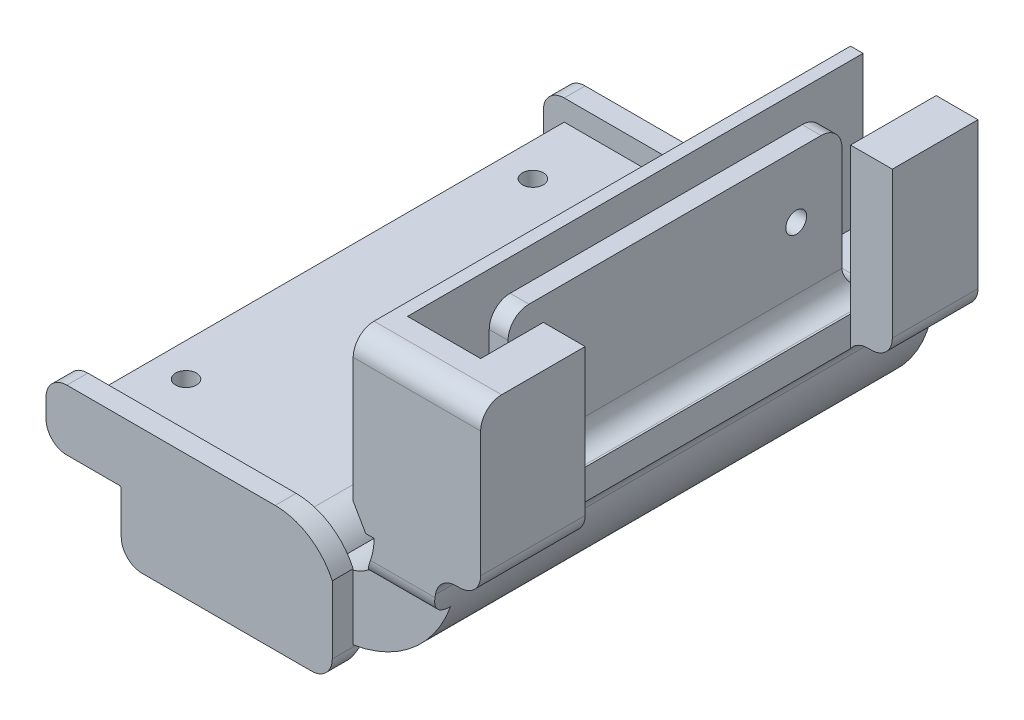
SolidWorks part; units mm, degrees
ref_plane "Alzado" through (0, 0, 0) normal (0, 0, 1) x (1, 0, 0)
ref_plane "Planta" through (0, 0, 0) normal (0, 1, 0) x (1, 0, 0)
ref_plane "Vista lateral" through (0, 0, 0) normal (1, 0, 0) x (0, 0, -1)
sketch "Croquis1" plane through (0, 0, 0) normal (0, 0, 1) x (1, 0, 0)
  line L0 (0, 0) -> (0, -5)
  line L1 (15, -20) -> (337, -20)
  line L2 (352, -5) -> (352, 0)
  line L3 (-15, 0) -> (-15, -5)
  line L4 (15, -35) -> (337, -35)
  line L5 (367, -5) -> (367, 0)
  line L6 (-15, 0) -> (0, 0)
  line L7 (352, 0) -> (367, 0)
  arc A0 (352, -5) -> (337, -20) centre (337, -5) cw
  arc A1 (0, -5) -> (15, -20) centre (15, -5) ccw
  arc A2 (-15, -5) -> (15, -35) centre (15, -5) ccw
  arc A3 (367, -5) -> (337, -35) centre (337, -5) cw
  dimension "D1" = 15
  dimension "D2" = 5
  dimension "D4" = 352
  dimension "D3" = 15
extrude "Saliente-Extruir1" add sketch "Croquis1" along normal blind 103
sketch "Croquis2" plane through (0, 0, 0) normal (0, 1, 0) x (1, 0, 0)
  line L0 (0, -103) -> (0, 0) construction
  line L1 (-10, -25.1459) -> (-5, -25.1459)
  line L2 (-10, -25.1459) -> (-10, -75.1459)
  line L3 (-10, -75.1459) -> (-5, -75.1459)
  line L4 (-5, -25.1459) -> (-5, -75.1459)
  line L5 (357, -11.55) -> (362, -11.55)
  line L6 (357, -11.55) -> (357, -91.45)
  line L7 (357, -91.45) -> (362, -91.45)
  line L8 (362, -11.55) -> (362, -91.45)
  line L9 (352, -103) -> (352, 0) construction
  line L10 (352, 0) -> (352, -103) construction
  point P12 (362, -51.5)
  point P17 (352, -51.5)
  dimension "D1" = 5
  dimension "D2" = 50
  dimension "D3" = 5
  dimension "D4" = 79.9
  dimension "D5" = 5
  dimension "D6" = 5
extrude "Saliente-Extruir2" add sketch "Croquis2" along normal blind 35
fillet "Redondeo1" radius 5 8 edges at (362, 0, 51.5) (359.5, 0, 91.45) (357, 0, 51.5) (359.5, 0, 11.55) (-7.5, 0, 25.1459) (-10, 0, 50.1459) (-7.5, 0, 75.1459) (-5, 0, 50.1459)
fillet "Redondeo2" radius 5 4 edges at (-7.5, 35, 25.1459) (-7.5, 35, 75.1459) (359.5, 35, 11.55) (359.5, 35, 91.45)
ref_plane "Plano1" through (15, 0, 0) normal (1, 0, 0) x (0, 0, -1)
sketch "Croquis3" plane through (15, 0, 0) normal (1, 0, 0) x (0, 0, -1)
  line L0 (-103, -35) -> (0, -35) construction
  line L1 (-76.5, -35) -> (-70.5, -35)
  line L2 (-76.5, -35) -> (-76.5, -43)
  line L3 (-76.5, -43) -> (-26.5, -43)
  line L4 (-26.5, -35) -> (-26.5, -43)
  line L5 (-103, -35) -> (-70.5, -35) construction
  line L6 (-51.5, -33) -> (-51.5, -5) construction
  line L7 (-103, -5) -> (0, -5) construction
  line L8 (-32.5, -35) -> (-26.5, -35)
  line L10 (-70.5, -35) -> (-70.5, -39)
  line L11 (-70.5, -39) -> (-32.5, -39)
  line L12 (-32.5, -35) -> (-32.5, -39)
  line L13 (-51.5, -35) -> (-32.5, -39) construction
  line L14 (-70.5, -39) -> (-51.5, -35) construction
  line L15 (-32.5, -35) -> (0, -35) construction
  dimension "D1" = 50
  dimension "D2" = 8
  dimension "D3" = 38
  dimension "D4" = 4
extrude "Saliente-Extruir3" add sketch "Croquis3" along normal up to vertex (322 mm away) up to point (337, -35, 103)
fillet "Redondeo4" radius 10 2 edges at (176, -35, 76.5) (176, -35, 26.5)
fillet "Redondeo5" radius 10 2 edges at (176, -43, 26.5) (176, -43, 76.5)
sketch "Croquis4" plane through (0, 0, 103) normal (0, 0, 1) x (1, 0, 0)
  line L0 (176, -43) -> (176, 89.8456) construction
  line L1 (337, -43) -> (15, -43) construction
  line L3 (176, 89.8456) -> (296, 89.8456)
  line L4 (176, 89.8456) -> (176, -75.5918)
  line L5 (176, -75.5918) -> (296, -75.5918)
  line L6 (296, 89.8456) -> (296, -75.5918)
  dimension "D1" = 120
extrude "Cortar-Extruir1" cut sketch "Croquis4" against normal through all both and the other way through all body kept at (296, -39, 24.702)
sketch "Croquis8" plane through (296, 0, 0) normal (-1, 0, 0) x (0, 0, 1)
  line L1 (103, -20) -> (0, -20)
  line L2 (103, -20) -> (103, -27)
  line L3 (103, -27) -> (0, -27)
  line L4 (0, -20) -> (0, -27)
  dimension "D1" = 7
extrude "Saliente-Extruir5" add sketch "Croquis8" along normal blind 200
fillet "Redondeo6" radius 15 2 edges at (96, -23.5, 0) (96, -23.5, 103)
sketch "Croquis9" plane through (0, -27, 0) normal (0, -1, 0) x (1, 0, 0)
  line L2 (96, 51.5) -> (106, 51.5) construction
  line L19 (96, 15) -> (96, 88) construction
  line L26 (144.6603, 56.5) -> (147.3397, 56.5)
  line L27 (124.6603, 46.5) -> (127.3397, 46.5)
  line L37 (124.6603, 56.5) -> (127.3397, 56.5)
  line L45 (144.6603, 46.5) -> (147.3397, 46.5)
  line L46 (204.6603, 56.5) -> (207.3397, 56.5)
  line L47 (164.6603, 56.5) -> (167.3397, 56.5)
  line L48 (164.6603, 46.5) -> (167.3397, 46.5)
  line L50 (184.6603, 56.5) -> (187.3397, 56.5)
  line L51 (184.6603, 46.5) -> (187.3397, 46.5)
  line L53 (204.6603, 46.5) -> (207.3397, 46.5)
  line L54 (224.6603, 46.5) -> (227.3397, 46.5)
  line L55 (224.6603, 56.5) -> (227.3397, 56.5)
  line L56 (244.6603, 46.5) -> (247.3397, 46.5)
  line L57 (244.6603, 56.5) -> (247.3397, 56.5)
  arc A33 (127.3397, 46.5) -> (144.6603, 46.5) centre (136, 51.5) ccw
  arc A34 (147.3397, 46.5) -> (164.6603, 46.5) centre (156, 51.5) ccw
  arc A35 (167.3397, 46.5) -> (184.6603, 46.5) centre (176, 51.5) ccw
  arc A36 (187.3397, 46.5) -> (204.6603, 46.5) centre (196, 51.5) ccw
  arc A38 (244.6603, 56.5) -> (227.3397, 56.5) centre (236, 51.5) ccw
  arc A39 (247.3397, 46.5) -> (247.3397, 56.5) centre (256, 51.5) ccw
  arc A41 (124.6603, 56.5) -> (124.6603, 46.5) centre (116, 51.5) ccw
  arc A42 (144.6603, 56.5) -> (127.3397, 56.5) centre (136, 51.5) ccw
  arc A43 (204.6603, 56.5) -> (187.3397, 56.5) centre (196, 51.5) ccw
  arc A44 (207.3397, 46.5) -> (224.6603, 46.5) centre (216, 51.5) ccw
  arc A45 (164.6603, 56.5) -> (147.3397, 56.5) centre (156, 51.5) ccw
  arc A46 (227.3397, 46.5) -> (244.6603, 46.5) centre (236, 51.5) ccw
  arc A47 (184.6603, 56.5) -> (167.3397, 56.5) centre (176, 51.5) ccw
  arc A49 (224.6603, 56.5) -> (207.3397, 56.5) centre (216, 51.5) ccw
  point P8 (186, 51.5)
  dimension "D2" = 20
sketch "Croquis10" plane through (362, 0, 0) normal (1, 0, 0) x (0, 0, -1)
  line L0 (-51.5, 35) -> (-51.5, 2.6584) construction
  line L1 (-86.45, 35) -> (-16.55, 35) construction
  line L2 (-80.5, 20) -> (-22.5, 20) construction
  circle A0 centre (-80.5, 20) radius 2.5
  circle A1 centre (-22.5, 20) radius 2.5
  point P4 (-51.5, 20)
  dimension "D1" = 58
  dimension "D3" = 5
  dimension "D4" = 5
  dimension "D2" = 15
extrude "Cortar-Extruir5" cut sketch "Croquis10" against normal through all
extrude "Cortar-Extruir6" cut sketch "Croquis9" against normal blind 10
sketch "Croquis11" plane through (0, -27, 0) normal (0, -1, 0) x (1, 0, 0)
  line L0 (247.3397, 56.5) -> (244.6603, 56.5) construction
  line L1 (244.6603, 46.5) -> (247.3397, 46.5) construction
  line L2 (227.3397, 56.5) -> (224.6603, 56.5) construction
  line L3 (224.6603, 46.5) -> (227.3397, 46.5) construction
  line L8 (96, 88) -> (96, 15)
  line L9 (111, 0) -> (296, 0)
  line L10 (296, 0) -> (296, 103)
  line L11 (296, 103) -> (111, 103)
  line L12 (96, 88) -> (96, 15)
  line L13 (111, 0) -> (296, 0)
  line L14 (296, 0) -> (296, 103)
  line L15 (296, 103) -> (111, 103)
  line L28 (207.3397, 56.5) -> (204.6603, 56.5) construction
  line L29 (204.6603, 46.5) -> (207.3397, 46.5) construction
  line L30 (184.6603, 46.5) -> (187.3397, 46.5) construction
  line L31 (187.3397, 56.5) -> (184.6603, 56.5) construction
  line L32 (164.6603, 46.5) -> (167.3397, 46.5) construction
  line L33 (167.3397, 56.5) -> (164.6603, 56.5) construction
  line L34 (147.3397, 56.5) -> (144.6603, 56.5) construction
  line L35 (144.6603, 46.5) -> (147.3397, 46.5) construction
  line L36 (124.6603, 46.5) -> (127.3397, 46.5) construction
  line L37 (127.3397, 56.5) -> (124.6603, 56.5) construction
  line L38 (247.3397, 56.5) -> (244.6603, 56.5)
  line L39 (244.6603, 46.5) -> (247.3397, 46.5)
  line L40 (227.3397, 56.5) -> (224.6603, 56.5)
  line L41 (224.6603, 46.5) -> (227.3397, 46.5)
  line L42 (207.3397, 56.5) -> (204.6603, 56.5)
  line L43 (204.6603, 46.5) -> (207.3397, 46.5)
  line L44 (184.6603, 46.5) -> (187.3397, 46.5)
  line L45 (187.3397, 56.5) -> (184.6603, 56.5)
  line L46 (164.6603, 46.5) -> (167.3397, 46.5)
  line L47 (167.3397, 56.5) -> (164.6603, 56.5)
  line L48 (147.3397, 56.5) -> (144.6603, 56.5)
  line L49 (144.6603, 46.5) -> (147.3397, 46.5)
  line L50 (124.6603, 46.5) -> (127.3397, 46.5)
  line L51 (127.3397, 56.5) -> (124.6603, 56.5)
  arc A0 (247.3397, 46.5) -> (247.3397, 56.5) centre (256, 51.5) ccw construction
  arc A1 (227.3397, 46.5) -> (244.6603, 46.5) centre (236, 51.5) ccw construction
  arc A4 (96, 15) -> (111, 0) centre (111, 15) ccw
  arc A5 (111, 103) -> (96, 88) centre (111, 88) ccw
  arc A6 (96, 15) -> (111, 0) centre (111, 15) ccw
  arc A7 (111, 103) -> (96, 88) centre (111, 88) ccw
  arc A22 (244.6603, 56.5) -> (227.3397, 56.5) centre (236, 51.5) ccw construction
  arc A23 (207.3397, 46.5) -> (224.6603, 46.5) centre (216, 51.5) ccw construction
  arc A24 (204.6603, 56.5) -> (187.3397, 56.5) centre (196, 51.5) ccw construction
  arc A25 (224.6603, 56.5) -> (207.3397, 56.5) centre (216, 51.5) ccw construction
  arc A26 (187.3397, 46.5) -> (204.6603, 46.5) centre (196, 51.5) ccw construction
  arc A27 (184.6603, 56.5) -> (167.3397, 56.5) centre (176, 51.5) ccw construction
  arc A28 (167.3397, 46.5) -> (184.6603, 46.5) centre (176, 51.5) ccw construction
  arc A29 (147.3397, 46.5) -> (164.6603, 46.5) centre (156, 51.5) ccw construction
  arc A30 (164.6603, 56.5) -> (147.3397, 56.5) centre (156, 51.5) ccw construction
  arc A31 (127.3397, 46.5) -> (144.6603, 46.5) centre (136, 51.5) ccw construction
  arc A32 (144.6603, 56.5) -> (127.3397, 56.5) centre (136, 51.5) ccw construction
  arc A33 (124.6603, 56.5) -> (124.6603, 46.5) centre (116, 51.5) ccw construction
  arc A34 (247.3397, 46.5) -> (247.3397, 56.5) centre (256, 51.5) ccw
  arc A35 (227.3397, 46.5) -> (244.6603, 46.5) centre (236, 51.5) ccw
  arc A36 (244.6603, 56.5) -> (227.3397, 56.5) centre (236, 51.5) ccw
  arc A37 (207.3397, 46.5) -> (224.6603, 46.5) centre (216, 51.5) ccw
  arc A38 (204.6603, 56.5) -> (187.3397, 56.5) centre (196, 51.5) ccw
  arc A39 (224.6603, 56.5) -> (207.3397, 56.5) centre (216, 51.5) ccw
  arc A40 (187.3397, 46.5) -> (204.6603, 46.5) centre (196, 51.5) ccw
  arc A41 (184.6603, 56.5) -> (167.3397, 56.5) centre (176, 51.5) ccw
  arc A42 (167.3397, 46.5) -> (184.6603, 46.5) centre (176, 51.5) ccw
  arc A43 (147.3397, 46.5) -> (164.6603, 46.5) centre (156, 51.5) ccw
  arc A44 (164.6603, 56.5) -> (147.3397, 56.5) centre (156, 51.5) ccw
  arc A45 (127.3397, 46.5) -> (144.6603, 46.5) centre (136, 51.5) ccw
  arc A46 (144.6603, 56.5) -> (127.3397, 56.5) centre (136, 51.5) ccw
  arc A47 (124.6603, 56.5) -> (124.6603, 46.5) centre (116, 51.5) ccw
  dimension "D1" = 0
extrude "Saliente-Extruir6" add sketch "Croquis11" against normal blind 12
sketch "Croquis12" plane through (296, 0, 0) normal (1, 0, 0) x (0, 0, -1)
  line L4 (-103, -20) -> (0, -20)
  line L5 (0, -20) -> (0, -15)
  line L6 (0, -15) -> (-103, -15)
  line L7 (-103, -15) -> (-103, -20)
  line L8 (-103, -20) -> (0, -20)
  line L9 (0, -20) -> (0, -15)
  line L10 (0, -15) -> (-103, -15)
  line L11 (-103, -15) -> (-103, -20)
  dimension "D1" = 0
extrude "Saliente-Extruir7" add sketch "Croquis12" along normal up to vertex (41 mm away) up to point (337, -20, 103)
fillet "Redondeo7" radius 10 1 edges at (337, -15, 51.5)
sketch "Croquis13" plane through (0, 0, 103) normal (0, 0, 1) x (1, 0, 0)
  line L1 (296, -27) -> (84.0172, -27)
  line L2 (296, -27) -> (296, -20)
  line L3 (296, -20) -> (84.0172, -20)
  line L4 (84.0172, -27) -> (84.0172, -20)
  dimension "D1" = 7
extrude "Cortar-Extruir7" cut sketch "Croquis13" against normal through all both and the other way through all
fillet "Redondeo8" radius 5 1 edges at (296, -20, 51.5)
sketch "Croquis14" plane through (0, -20, 0) normal (0, -1, 0) x (1, 0, 0)
  line L0 (291, 0) -> (111, 0) construction
  line L1 (291, 103) -> (266, 103) construction
  line L2 (291, 103) -> (291, 0) construction
  line L3 (291, 0) -> (266, 0) construction
  line L4 (266, 103) -> (266, 0) construction
  line L5 (278.5, 103) -> (278.5, 0) construction
  line L7 (278.5, 103) -> (88.221, 103)
  line L8 (278.5, 103) -> (278.5, -5.9563)
  line L9 (278.5, -5.9563) -> (88.221, -5.9563)
  line L10 (88.221, 103) -> (88.221, -5.9563)
  arc A0 (247.3397, 46.5) -> (247.3397, 56.5) centre (256, 51.5) ccw construction
extrude "Cortar-Extruir8" cut sketch "Croquis14" against normal blind 10
sketch "Croquis15" plane through (0, -20, 0) normal (0, -1, 0) x (1, 0, 0)
  line L0 (286.5, 103) -> (286.5, 0) construction
  line L1 (291, 103) -> (278.5, 103) construction
  line L2 (291, 0) -> (278.5, 0) construction
  line L3 (278.5, 103) -> (278.5, 0) construction
  circle A0 centre (286.5, 93) radius 2.5
  circle A1 centre (286.5, 10) radius 2.5
  dimension "D1" = 5
  dimension "D2" = 5
  dimension "D3" = 8
  dimension "D4" = 10
  dimension "D5" = 10
extrude "Cortar-Extruir9" cut sketch "Croquis15" against normal through all both and the other way through all
sketch "Croquis16" plane through (357, 0, 0) normal (-1, 0, 0) x (0, 0, 1)
  line L4 (86.45, 35) -> (16.55, 35)
  line L5 (11.55, 30) -> (11.55, 5)
  line L6 (11.55, 5) -> (91.45, 5)
  line L7 (91.45, 5) -> (91.45, 30)
  line L8 (86.45, 35) -> (16.55, 35)
  line L9 (11.55, 30) -> (11.55, 5)
  line L10 (11.55, 5) -> (91.45, 5)
  line L11 (91.45, 5) -> (91.45, 30)
  arc A2 (16.55, 35) -> (11.55, 30) centre (16.55, 30) ccw
  arc A3 (91.45, 30) -> (86.45, 35) centre (86.45, 30) ccw
  arc A4 (16.55, 35) -> (11.55, 30) centre (16.55, 30) ccw
  arc A5 (91.45, 30) -> (86.45, 35) centre (86.45, 30) ccw
  dimension "D1" = 0
extrude "Cortar-Extruir10" cut sketch "Croquis16" against normal blind 0.5
sketch "Croquis17" plane through (0, 0, 0) normal (0, 0, -1) x (-1, 0, 0)
  line L0 (-296, -43) -> (-296, -39) construction
  line L1 (-296, -39) -> (-296, -35) construction
  line L2 (-296, -35) -> (-296, -25) construction
  line L3 (-291, -20) -> (-278.5, -20) construction
  line L4 (-296, -43) -> (-296, -39)
  line L5 (-296, -39) -> (-296, -35)
  line L6 (-296, -35) -> (-296, -25)
  line L7 (-291, -20) -> (-278.5, -20)
  line L8 (-296.5, -43) -> (-296.5, -39)
  line L9 (-296.5, -39) -> (-296.5, -35)
  line L10 (-296.5, -35) -> (-296.5, -25)
  line L11 (-291, -19.5) -> (-278.5, -19.5)
  line L12 (-278.5, -19.5) -> (-278.5, -20)
  line L13 (-296.5, -43) -> (-296, -43)
  arc A0 (-291, -20) -> (-296, -25) centre (-291, -25) ccw construction
  arc A1 (-291, -20) -> (-296, -25) centre (-291, -25) ccw
  arc A2 (-291, -19.5) -> (-296.5, -25) centre (-291, -25) ccw
  dimension "D1" = 0.5
extrude "Cortar-Extruir11" cut sketch "Croquis17" against normal through all both and the other way through all
sketch "Croquis18" plane through (0, 0, 103) normal (0, 0, 1) x (1, 0, 0)
  line L8 (296.5, -25) -> (296.5, -35)
  line L9 (296.5, -35) -> (337, -35)
  line L10 (367, -5) -> (367, 0)
  line L11 (367, 0) -> (352, 0)
  line L12 (352, 0) -> (352, -5)
  line L13 (328.3397, -15) -> (278.5, -15)
  line L14 (278.5, -15) -> (278.5, -19.5)
  line L15 (278.5, -19.5) -> (291, -19.5)
  line L16 (296.5, -25) -> (296.5, -35)
  line L17 (296.5, -35) -> (337, -35)
  line L18 (367, -5) -> (367, 0)
  line L19 (367, 0) -> (352, 0)
  line L20 (352, 0) -> (352, -5)
  line L21 (328.3397, -15) -> (278.5, -15)
  line L22 (278.5, -15) -> (278.5, -19.5)
  line L23 (278.5, -19.5) -> (291, -19.5)
  arc A4 (337, -35) -> (367, -5) centre (337, -5) ccw
  arc A5 (337, -20) -> (352, -5) centre (337, -5) ccw
  arc A6 (337, -20) -> (328.3397, -15) centre (328.3397, -25) ccw
  arc A7 (296.5, -25) -> (291, -19.5) centre (291, -25) ccw
  arc A8 (337, -35) -> (367, -5) centre (337, -5) ccw
  arc A9 (337, -20) -> (352, -5) centre (337, -5) ccw
  arc A10 (337, -20) -> (328.3397, -15) centre (328.3397, -25) ccw
  arc A11 (296.5, -25) -> (291, -19.5) centre (291, -25) ccw
  dimension "D1" = 0
extrude "Saliente-Extruir8" add sketch "Croquis18" along normal blind 0.5
sketch "Croquis19" plane through (0, 0, 103.5) normal (0, 0, 1) x (1, 0, 0)
  line L0 (348.1803, -15) -> (365.2843, -15)
  line L1 (352, 35) -> (367, 35)
  line L2 (367, 0) -> (352, 0) construction
  line L8 (296.5, -25) -> (296.5, -35)
  line L9 (296.5, -35) -> (337, -35)
  line L10 (367, -5) -> (367, 0)
  line L11 (367, 0) -> (352, 0)
  line L12 (352, 0) -> (352, -5)
  line L13 (328.3397, -15) -> (278.5, -15)
  line L14 (278.5, -15) -> (278.5, -19.5)
  line L15 (278.5, -19.5) -> (291, -19.5)
  line L18 (367, -5) -> (367, 35)
  line L20 (352, 35) -> (352, -5)
  arc A4 (296.5, -25) -> (291, -19.5) centre (291, -25) ccw
  arc A5 (337, -35) -> (367, -5) centre (337, -5) ccw
  arc A6 (337, -20) -> (352, -5) centre (337, -5) ccw
  arc A7 (337, -20) -> (328.3397, -15) centre (328.3397, -25) ccw
  arc A9 (365.2843, -15) -> (367, -5) centre (337, -5) ccw
  arc A10 (348.1803, -15) -> (352, -5) centre (337, -5) ccw
  dimension "D2" = 35
  dimension "D3" = 15
  dimension "D1" = 0
extrude "Saliente-Extruir9" add sketch "Croquis19" along normal blind 10
fillet "Redondeo22" radius 5 3 edges at (359.5, 35, 113.5) (356.7323, -15, 113.5) (359.5, 0, 103.5)
sketch "Croquis20" plane through (367, 0, 0) normal (1, 0, 0) x (0, 0, -1)
  line L8 (-103.5, 35) -> (-108.5, 35)
  line L9 (-113.5, 30) -> (-113.5, -5)
  line L10 (-113.5, -5) -> (0, -5)
  line L11 (0, -5) -> (0, 0)
  line L12 (0, 0) -> (-6.55, 0)
  line L13 (-6.55, 0) -> (-96.45, 0)
  line L14 (-96.45, 0) -> (-98.5, 0)
  line L15 (-103.5, 5) -> (-103.5, 35)
  line L16 (-103.5, 35) -> (-108.5, 35)
  line L17 (-113.5, 30) -> (-113.5, -5)
  line L18 (-113.5, -5) -> (0, -5)
  line L19 (0, -5) -> (0, 0)
  line L20 (0, 0) -> (-6.55, 0)
  line L21 (-6.55, 0) -> (-96.45, 0)
  line L22 (-96.45, 0) -> (-98.5, 0)
  line L23 (-103.5, 5) -> (-103.5, 35)
  arc A2 (-108.5, 35) -> (-113.5, 30) centre (-108.5, 30) ccw
  arc A3 (-108.5, 35) -> (-113.5, 30) centre (-108.5, 30) ccw
  arc A6 (-103.5, 5) -> (-98.5, 0) centre (-98.5, 5) ccw
  arc A7 (-103.5, 5) -> (-98.5, 0) centre (-98.5, 5) ccw
  dimension "D1" = 0
extrude "Saliente-Extruir10" add sketch "Croquis20" along normal blind 0.5
sketch "Croquis21" plane through (367.5, 0, 0) normal (1, 0, 0) x (0, 0, -1)
  line L1 (-103.5, 35) -> (-88.5, 35)
  line L4 (-88.5, 35) -> (-88.5, -5)
  line L6 (-103.5, 35) -> (-108.5, 35) construction
  line L8 (0, 0) -> (0, 35)
  line L9 (0, 35) -> (-15, 35)
  line L10 (-15, -5) -> (-15, 35)
  line L11 (-15, -5) -> (0, -5)
  line L17 (-103.5, 5) -> (-103.5, 35)
  line L18 (-103.5, 35) -> (-108.5, 35)
  line L19 (-113.5, 30) -> (-113.5, -5)
  line L20 (-113.5, -5) -> (0, -5)
  line L21 (0, -5) -> (0, 0)
  line L22 (0, 0) -> (-98.5, 0)
  line L24 (-103.5, 35) -> (-108.5, 35)
  line L25 (-113.5, 30) -> (-113.5, -5)
  line L26 (-113.5, -5) -> (-88.5, -5)
  line L27 (0, -5) -> (0, 0)
  arc A2 (-108.5, 35) -> (-113.5, 30) centre (-108.5, 30) ccw
  arc A3 (-108.5, 35) -> (-113.5, 30) centre (-108.5, 30) ccw
  arc A5 (-103.5, 5) -> (-98.5, 0) centre (-98.5, 5) ccw
  dimension "D1" = 15
  dimension "D2" = 15
  dimension "D3" = 0
extrude "Saliente-Extruir11" add sketch "Croquis21" along normal blind 10
fillet "Redondeo13" radius 5 3 edges at (367, -5, 56.75) (377.5, -5, 7.5) (377.5, -5, 101)
sketch "Croquis22" plane through (352, 0, 0) normal (-1, 0, 0) x (0, 0, 1)
  line L8 (113.5, -5) -> (113.5, 30)
  line L9 (108.5, 35) -> (103.5, 35)
  line L10 (103.5, 35) -> (103.5, 5)
  line L11 (98.5, 0) -> (96.45, 0)
  line L12 (96.45, 0) -> (6.55, 0)
  line L13 (6.55, 0) -> (0, 0)
  line L14 (0, 0) -> (0, -5)
  line L15 (0, -5) -> (113.5, -5)
  line L16 (113.5, -5) -> (113.5, 30)
  line L17 (108.5, 35) -> (103.5, 35)
  line L18 (103.5, 35) -> (103.5, 5)
  line L19 (98.5, 0) -> (96.45, 0)
  line L20 (96.45, 0) -> (6.55, 0)
  line L21 (6.55, 0) -> (0, 0)
  line L22 (0, 0) -> (0, -5)
  line L23 (0, -5) -> (113.5, -5)
  arc A2 (113.5, 30) -> (108.5, 35) centre (108.5, 30) ccw
  arc A3 (113.5, 30) -> (108.5, 35) centre (108.5, 30) ccw
  arc A6 (98.5, 0) -> (103.5, 5) centre (98.5, 5) ccw
  arc A7 (98.5, 0) -> (103.5, 5) centre (98.5, 5) ccw
  dimension "D1" = 0
extrude "Saliente-Extruir12" add sketch "Croquis22" along normal blind 2
sketch "Croquis23" plane through (350, 0, 0) normal (-1, 0, 0) x (0, 0, 1)
  line L1 (113.5, -5) -> (0, -5)
  line L2 (113.5, -5) -> (113.5, 30)
  line L3 (108.5, 35) -> (0, 35)
  line L4 (0, -5) -> (0, 35)
  arc A0 (113.5, 30) -> (108.5, 35) centre (108.5, 30) ccw construction
  arc A1 (113.5, 30) -> (108.5, 35) centre (108.5, 30) ccw
extrude "Saliente-Extruir13" add sketch "Croquis23" along normal blind 3
chamfer "Chaflán1" distance 3 angle 60 1 edges at (347, -5, 56.75) first distance on face at (349.5, -5, 56.75)
sketch "Croquis25" plane through (0, 0, 0) normal (0, 0, -1) x (-1, 0, 0)
  line L15 (-352, -5) -> (-350, -5)
  line L16 (-350, -5) -> (-347, 0.1962)
  line L17 (-347, 0.1962) -> (-347, 35)
  line L18 (-347, 35) -> (-350, 35)
  line L19 (-350, 35) -> (-350, 0)
  line L20 (-350, 0) -> (-367.5, 0)
  line L21 (-367.5, 0) -> (-367.5, 35)
  line L22 (-367.5, 35) -> (-377.5, 35)
  line L23 (-377.5, 35) -> (-377.5, 0)
  line L24 (-372.5, -5) -> (-371.641, -5)
  line L25 (-337, -35) -> (-296.5, -35)
  line L26 (-296.5, -35) -> (-296.5, -25)
  line L27 (-291, -19.5) -> (-278.5, -19.5)
  line L28 (-278.5, -19.5) -> (-278.5, -15)
  line L29 (-278.5, -15) -> (-328.3397, -15)
  line L30 (-352, -5) -> (-350, -5)
  line L31 (-350, -5) -> (-347, 0.1962)
  line L32 (-347, 0.1962) -> (-347, 35)
  line L33 (-347, 35) -> (-350, 35)
  line L34 (-350, 35) -> (-350, 0)
  line L35 (-350, 0) -> (-367.5, 0)
  line L36 (-367.5, 0) -> (-367.5, 35)
  line L37 (-367.5, 35) -> (-377.5, 35)
  line L38 (-377.5, 35) -> (-377.5, 0)
  line L39 (-372.5, -5) -> (-371.641, -5)
  line L40 (-337, -35) -> (-296.5, -35)
  line L41 (-296.5, -35) -> (-296.5, -25)
  line L42 (-291, -19.5) -> (-278.5, -19.5)
  line L43 (-278.5, -19.5) -> (-278.5, -15)
  line L44 (-278.5, -15) -> (-328.3397, -15)
  arc A6 (-377.5, 0) -> (-372.5, -5) centre (-372.5, 0) ccw
  arc A7 (-366.6923, -9.2857) -> (-371.641, -5) centre (-371.641, -10) ccw
  arc A8 (-366.6923, -9.2857) -> (-337, -35) centre (-337, -5) ccw
  arc A9 (-291, -19.5) -> (-296.5, -25) centre (-291, -25) ccw
  arc A10 (-328.3397, -15) -> (-337, -20) centre (-328.3397, -25) ccw
  arc A11 (-352, -5) -> (-337, -20) centre (-337, -5) ccw
  arc A12 (-377.5, 0) -> (-372.5, -5) centre (-372.5, 0) ccw
  arc A13 (-366.6923, -9.2857) -> (-371.641, -5) centre (-371.641, -10) ccw
  arc A14 (-366.6923, -9.2857) -> (-337, -35) centre (-337, -5) ccw
  arc A15 (-291, -19.5) -> (-296.5, -25) centre (-291, -25) ccw
  arc A16 (-328.3397, -15) -> (-337, -20) centre (-328.3397, -25) ccw
  arc A17 (-352, -5) -> (-337, -20) centre (-337, -5) ccw
  dimension "D1" = 0
extrude "Saliente-Extruir14" add sketch "Croquis25" along normal blind 0.5
sketch "Croquis26" plane through (0, 0, 103.5) normal (0, 0, 1) x (1, 0, 0)
  line L6 (365.2843, -15) -> (348.1803, -15)
  line L7 (328.3397, -15) -> (278.5, -15)
  line L8 (278.5, -15) -> (278.5, -19.5)
  line L9 (278.5, -19.5) -> (291, -19.5)
  line L10 (296.5, -25) -> (296.5, -35)
  line L11 (296.5, -35) -> (337, -35)
  line L13 (328.3397, -15) -> (278.5, -15)
  line L14 (278.5, -15) -> (278.5, -19.5)
  line L15 (278.5, -19.5) -> (291, -19.5)
  line L16 (296.5, -25) -> (296.5, -35)
  line L17 (296.5, -35) -> (337, -35)
  line L20 (365.2843, -15) -> (348.1803, -15)
  arc A3 (337, -35) -> (365.2843, -15) centre (337, -5) ccw
  arc A4 (337, -20) -> (328.3397, -15) centre (328.3397, -25) ccw
  arc A5 (296.5, -25) -> (291, -19.5) centre (291, -25) ccw
  arc A6 (337, -35) -> (365.2843, -15) centre (337, -5) ccw
  arc A7 (337, -20) -> (328.3397, -15) centre (328.3397, -25) ccw
  arc A8 (296.5, -25) -> (291, -19.5) centre (291, -25) ccw
  arc A10 (337, -20) -> (348.1803, -15) centre (337, -5) ccw
  arc A11 (337, -20) -> (348.1803, -15) centre (337, -5) ccw
  dimension "D1" = 0
extrude "Saliente-Extruir15" add sketch "Croquis26" along normal blind 5
sketch "Croquis27" plane through (0, 0, -0.5) normal (0, 0, -1) x (-1, 0, 0)
  line L15 (-352, -5) -> (-350, -5)
  line L16 (-350, -5) -> (-347, 0.1962)
  line L17 (-347, 0.1962) -> (-347, 35)
  line L18 (-347, 35) -> (-350, 35)
  line L19 (-350, 35) -> (-350, 0)
  line L20 (-350, 0) -> (-367.5, 0)
  line L21 (-367.5, 0) -> (-367.5, 35)
  line L22 (-367.5, 35) -> (-377.5, 35)
  line L23 (-377.5, 35) -> (-377.5, 0)
  line L24 (-372.5, -5) -> (-371.641, -5)
  line L25 (-337, -35) -> (-296.5, -35)
  line L26 (-296.5, -35) -> (-296.5, -25)
  line L27 (-291, -19.5) -> (-278.5, -19.5)
  line L28 (-278.5, -19.5) -> (-278.5, -15)
  line L29 (-278.5, -15) -> (-328.3397, -15)
  line L30 (-352, -5) -> (-350, -5)
  line L31 (-350, -5) -> (-347, 0.1962)
  line L32 (-347, 0.1962) -> (-347, 35)
  line L33 (-347, 35) -> (-350, 35)
  line L34 (-350, 35) -> (-350, 0)
  line L35 (-350, 0) -> (-367.5, 0)
  line L36 (-367.5, 0) -> (-367.5, 35)
  line L37 (-367.5, 35) -> (-377.5, 35)
  line L38 (-377.5, 35) -> (-377.5, 0)
  line L39 (-372.5, -5) -> (-371.641, -5)
  line L40 (-337, -35) -> (-296.5, -35)
  line L41 (-296.5, -35) -> (-296.5, -25)
  line L42 (-291, -19.5) -> (-278.5, -19.5)
  line L43 (-278.5, -19.5) -> (-278.5, -15)
  line L44 (-278.5, -15) -> (-328.3397, -15)
  arc A6 (-352, -5) -> (-337, -20) centre (-337, -5) ccw
  arc A7 (-377.5, 0) -> (-372.5, -5) centre (-372.5, 0) ccw
  arc A8 (-366.6923, -9.2857) -> (-371.641, -5) centre (-371.641, -10) ccw
  arc A9 (-366.6923, -9.2857) -> (-337, -35) centre (-337, -5) ccw
  arc A10 (-291, -19.5) -> (-296.5, -25) centre (-291, -25) ccw
  arc A11 (-328.3397, -15) -> (-337, -20) centre (-328.3397, -25) ccw
  arc A12 (-352, -5) -> (-337, -20) centre (-337, -5) ccw
  arc A13 (-377.5, 0) -> (-372.5, -5) centre (-372.5, 0) ccw
  arc A14 (-366.6923, -9.2857) -> (-371.641, -5) centre (-371.641, -10) ccw
  arc A15 (-366.6923, -9.2857) -> (-337, -35) centre (-337, -5) ccw
  arc A16 (-291, -19.5) -> (-296.5, -25) centre (-291, -25) ccw
  arc A17 (-328.3397, -15) -> (-337, -20) centre (-328.3397, -25) ccw
  dimension "D1" = 0
extrude "Saliente-Extruir16" add sketch "Croquis27" along normal blind 5
sketch "Croquis28" plane through (0, 0, 108.5) normal (0, 0, 1) x (1, 0, 0)
  line L0 (337, -20) -> (337, -35) construction
  line L1 (328.3397, -10) -> (273.5, -10)
  line L2 (273.5, -10) -> (273.5, -24.5)
  line L3 (273.5, -24.5) -> (291, -24.5)
  line L4 (291.5, -25) -> (291.5, -40)
  line L5 (291.5, -40) -> (342, -40)
  line L6 (365.2843, -15) -> (348.1803, -15)
  line L7 (328.3397, -15) -> (278.5, -15)
  line L8 (278.5, -15) -> (278.5, -19.5)
  line L9 (278.5, -19.5) -> (291, -19.5)
  line L10 (296.5, -25) -> (296.5, -35)
  line L11 (296.5, -35) -> (337, -35)
  line L13 (328.3397, -15) -> (278.5, -15) construction
  line L14 (278.5, -15) -> (278.5, -19.5) construction
  line L15 (278.5, -19.5) -> (291, -19.5) construction
  line L16 (296.5, -25) -> (296.5, -35) construction
  line L17 (296.5, -35) -> (337, -35) construction
  line L18 (342, -18.8034) -> (342, -40)
  arc A0 (342, -18.8034) -> (328.3397, -10) centre (328.3397, -25) ccw
  arc A1 (291.5, -25) -> (291, -24.5) centre (291, -25) ccw
  arc A3 (337, -35) -> (365.2843, -15) centre (337, -5) ccw
  arc A4 (337, -20) -> (328.3397, -15) centre (328.3397, -25) ccw
  arc A5 (296.5, -25) -> (291, -19.5) centre (291, -25) ccw
  arc A7 (337, -20) -> (328.3397, -15) centre (328.3397, -25) ccw construction
  arc A8 (296.5, -25) -> (291, -19.5) centre (291, -25) ccw construction
  arc A12 (337, -20) -> (348.1803, -15) centre (337, -5) ccw
  dimension "D1" = 0
  dimension "D2" = 5
extrude "Saliente-Extruir17" add sketch "Croquis28" along normal blind 5
sketch "Croquis29" plane through (0, 0, -5.5) normal (0, 0, -1) x (-1, 0, 0)
  line L6 (-273.5, -10) -> (-328.3397, -10)
  line L7 (-273.5, -24.5) -> (-273.5, -10)
  line L8 (-291, -24.5) -> (-273.5, -24.5)
  line L9 (-291.5, -40) -> (-291.5, -25)
  line L10 (-342, -40) -> (-291.5, -40)
  line L11 (-342, -18.8034) -> (-342, -40)
  line L12 (-273.5, -10) -> (-328.3397, -10)
  line L13 (-273.5, -24.5) -> (-273.5, -10)
  line L14 (-291, -24.5) -> (-273.5, -24.5)
  line L15 (-291.5, -40) -> (-291.5, -25)
  line L16 (-342, -40) -> (-291.5, -40)
  line L17 (-342, -18.8034) -> (-342, -40)
  arc A2 (-328.3397, -10) -> (-342, -18.8034) centre (-328.3397, -25) ccw
  arc A3 (-291, -24.5) -> (-291.5, -25) centre (-291, -25) ccw
  arc A4 (-328.3397, -10) -> (-342, -18.8034) centre (-328.3397, -25) ccw
  arc A5 (-291, -24.5) -> (-291.5, -25) centre (-291, -25) ccw
  dimension "D1" = 0
extrude "Saliente-Extruir18" add sketch "Croquis29" along normal blind 5
fillet "Redondeo23" radius 5 8 edges at (273.5, -10, -8) (273.5, -24.5, -8) (291.5, -40, -8) (342, -40, -8) (273.5, -10, 111) (273.5, -24.5, 111) (291.5, -40, 111) (342, -40, 111)
sketch "Croquis31" plane through (0, -43, 0) normal (0, -1, 0) x (1, 0, 0)
  line L1 (296.5, 108.5) -> (337, 108.5)
  line L2 (296.5, 108.5) -> (296.5, -5.5)
  line L3 (296.5, -5.5) -> (337, -5.5)
  line L4 (337, 108.5) -> (337, -5.5)
extrude "Cortar-Extruir13" cut sketch "Croquis31" against normal up to surface (8 mm away) up to face at (316.75, -35, 51.5)
fillet "Redondeo24" radius 5 4 edges at (339.5088, -34.8949, -5.5) (339.5088, -34.8949, 108.5) (316.75, -35, -5.5) (316.75, -35, 108.5)
